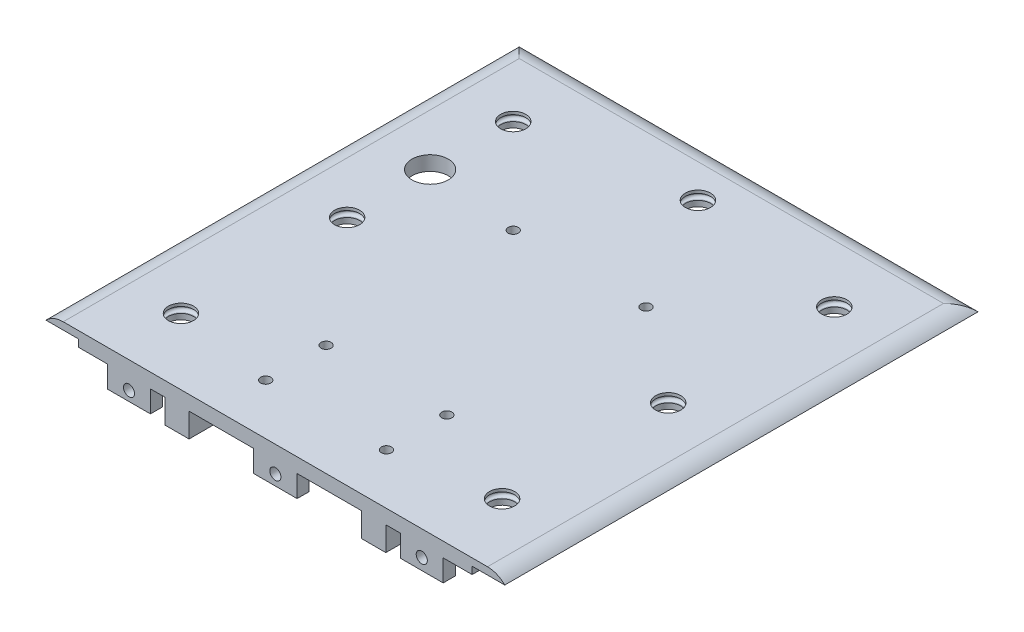
SolidWorks part; units mm, degrees
ref_plane "Спереди" through (0, 0, 0) normal (0, 0, 1) x (1, 0, 0)
ref_plane "Сверху" through (0, 0, 0) normal (0, 1, 0) x (1, 0, 0)
ref_plane "Справа" through (0, 0, 0) normal (1, 0, 0) x (0, 0, -1)
sketch "Эскиз1" plane through (0, 0, 0) normal (0, 1, 0) x (1, 0, 0)
  line L1 (0, 0) -> (190, 0)
  line L2 (0, 0) -> (0, 196)
  line L3 (0, 196) -> (190, 196)
  line L4 (190, 0) -> (190, 196)
  dimension "D1" = 196
  dimension "D2" = 190
extrude "Бобышка-Вытянуть1" add sketch "Эскиз1" along normal blind 3
fillet "Скругление1" radius 10 3 edges at (95, 3, -196) (190, 3, -98) (0, 3, -98)
sketch "Эскиз2" plane through (0, 0, 0) normal (0, -1, 0) x (1, 0, 0)
  line L1 (13.5, 0) -> (176.5, 0)
  line L2 (13.5, 0) -> (13.5, -187)
  line L3 (13.5, -187) -> (176.5, -187)
  line L4 (176.5, 0) -> (176.5, -187)
  line L5 (0, 0) -> (13.5, 0) construction
  line L6 (176.5, 0) -> (190, 0) construction
  dimension "D1" = 163
  dimension "D2" = 187
extrude "Бобышка-Вытянуть2" add sketch "Эскиз2" along normal blind 3
sketch "Эскиз3" plane through (0, -3, 0) normal (0, -1, 0) x (1, 0, 0)
  line L4 (54.25, 0) -> (54.25, -108.85) construction
  line L5 (135.75, 0) -> (135.75, -108.85) construction
  line L7 (49.25, -108.85) -> (59.25, -108.85)
  line L8 (49.25, -108.85) -> (49.25, 0)
  line L9 (49.25, 0) -> (59.25, 0)
  line L10 (59.25, -108.85) -> (59.25, 0)
  line L11 (49.25, -108.85) -> (59.25, 0) construction
  line L12 (49.25, 0) -> (59.25, -108.85) construction
  line L19 (130.75, -108.85) -> (140.75, -108.85)
  line L20 (130.75, -108.85) -> (130.75, 0)
  line L21 (130.75, 0) -> (140.75, 0)
  line L22 (140.75, -108.85) -> (140.75, 0)
  line L23 (130.75, -108.85) -> (140.75, 0) construction
  line L24 (130.75, 0) -> (140.75, -108.85) construction
  point P13 (54.25, -54.425)
  point P22 (135.75, -54.425)
  dimension "D1" = 108.85
  dimension "D2" = 10
extrude "Бобышка-Вытянуть3" add sketch "Эскиз3" along normal blind 10
sketch "Эскиз4" plane through (0, -3, 0) normal (0, -1, 0) x (1, 0, 0)
  line L0 (49.25, 0) -> (13.5, 0) construction
  line L1 (43.25, 0) -> (25.5, 0)
  line L2 (43.25, 0) -> (43.25, -5)
  line L3 (43.25, -5) -> (25.5, -5)
  line L4 (25.5, 0) -> (25.5, -5)
  line L11 (130.75, 0) -> (59.25, 0) construction
  line L12 (86, 0) -> (104, 0)
  line L13 (86, 0) -> (86, -5)
  line L14 (86, -5) -> (104, -5)
  line L15 (104, 0) -> (104, -5)
  line L16 (176.5, 0) -> (140.75, 0) construction
  line L17 (146.75, 0) -> (164.5, 0)
  line L18 (146.75, 0) -> (146.75, -5)
  line L19 (146.75, -5) -> (164.5, -5)
  line L20 (164.5, 0) -> (164.5, -5)
  line L22 (140.75, -108.85) -> (140.75, 0) construction
  line L23 (130.75, 0) -> (130.75, -108.85) construction
  line L27 (49.25, 0) -> (49.25, -108.85) construction
  line L28 (13.5, 0) -> (13.5, -187) construction
  line L29 (176.5, -187) -> (176.5, 0) construction
  dimension "D1" = 5
  dimension "D2" = 6
  dimension "D3" = 26.75
  dimension "D4" = 18
  dimension "D7" = 6
  dimension "D8" = 12
  dimension "D9" = 12
extrude "Бобышка-Вытянуть4" add sketch "Эскиз4" along normal blind 9
sketch "Эскиз5" plane through (0, 0, 0) normal (0, 0, 1) x (1, 0, 0)
  line L0 (34.375, -12) -> (34.375, -8) construction
  line L1 (43.25, -12) -> (25.5, -12) construction
  line L2 (34.375, -8) -> (161.3004, -7.2587) construction
  line L3 (155.625, -12) -> (155.625, -7.2919) construction
  line L4 (164.5, -12) -> (146.75, -12) construction
  line L5 (95, -12) -> (95, -7.6459) construction
  line L6 (104, -12) -> (86, -12) construction
  circle A1 centre (95, -7.6459) radius 2.3
  circle A2 centre (155.625, -7.2919) radius 2.3
  circle A3 centre (34.375, -8) radius 2.3
  dimension "D1" = 4.6
  dimension "D2" = 4
extrude "Вырез-Вытянуть1" cut sketch "Эскиз5" against normal blind 9
sketch "Эскиз6" plane through (49.25, 0, 0) normal (-1, 0, 0) x (0, 0, 1)
  line L0 (-108.85, -13) -> (-108.85, -9) construction
  line L1 (-108.85, -13) -> (-108.85, -3) construction
  line L2 (-108.85, -9) -> (-93.85, -9) construction
  circle A0 centre (-93.85, -9) radius 2.3
  circle A1 centre (-53.85, -9) radius 2.3
  circle A3 centre (-13.85, -9) radius 2.3 [skipped]
  dimension "D3" = 4.6
  dimension "D1" = 4
  dimension "D2" = 15
  dimension "D4" = 3
extrude "Вырез-Вытянуть2" cut sketch "Эскиз6" against normal blind 230
fillet "Скругление2" radius 2 1 edges at (95, -3, -187)
sketch "Эскиз8" plane through (0, -3, 0) normal (0, -1, 0) x (1, 0, 0)
  line L0 (95, -185) -> (95, -175) construction
  line L1 (13.5, -185) -> (176.5, -185) construction
  line L2 (13.5, -165) -> (28.5, -165) construction
  line L3 (13.5, 0) -> (13.5, -187) construction
  line L4 (13.5, -96.2) -> (28.5, -96.2) construction
  line L5 (13.5, 0) -> (13.5, -185) construction
  line L6 (13.5, -27.4) -> (28.5, -27.4) construction
  line L7 (176.5, -27.4) -> (161.5, -27.4) construction
  line L8 (176.5, -185) -> (176.5, 0) construction
  line L9 (176.5, -96.2) -> (161.5, -96.2) construction
  line L10 (176.5, -187) -> (176.5, 0) construction
  line L11 (176.5, -165) -> (161.5, -165) construction
  circle A0 centre (28.5, -27.4) radius 5.2
  circle A1 centre (28.5, -96.2) radius 5.2
  circle A2 centre (28.5, -165) radius 5.2
  circle A3 centre (95, -175) radius 5.2
  circle A4 centre (161.5, -165) radius 5.2
  circle A5 centre (161.5, -96.2) radius 5.2
  circle A6 centre (161.5, -27.4) radius 5.2
  dimension "D5" = 10.4
  dimension "D1" = 20
  dimension "D2" = 10
  dimension "D3" = 68.8
  dimension "D4" = 68.8
  dimension "D6" = 20
  dimension "D7" = 15
extrude "Вырез-Вытянуть3" cut sketch "Эскиз8" against normal blind 10
sketch "Эскиз9" plane through (0, 3, 0) normal (0, 1, 0) x (1, 0, 0)
  circle A0 centre (28.5, 27.4) radius 6.7
  circle A1 centre (28.5, 96.2) radius 6.7
  circle A2 centre (28.5, 165) radius 6.7
  circle A3 centre (95, 175) radius 6.7
  circle A4 centre (161.5, 165) radius 6.7
  circle A5 centre (161.5, 96.2) radius 6.7
  circle A6 centre (161.5, 27.4) radius 6.7
  dimension "D1" = 13.4
extrude "Вырез-Вытянуть4" cut sketch "Эскиз9" against normal blind 2.5 from offset 1.2 offset against normal yes
fillet "Скругление3" radius 1.2 14 edges at (161.5, 1.8, -89.5) (161.5, 1.8, -158.3) (95, 1.8, -168.3) (28.5, 1.8, -158.3) (28.5, 1.8, -89.5) (28.5, 1.8, -20.7) (161.5, 1.8, -20.7) (28.5, -0.7, -20.7) (28.5, -0.7, -89.5) (28.5, -0.7, -158.3) (95, -0.7, -168.3) (161.5, -0.7, -158.3) (161.5, -0.7, -89.5) (161.5, -0.7, -20.7)
sketch "Эскиз10" plane through (0, 0, 0) normal (0, -1, 0) x (1, 0, 0)
  line L0 (13.5, 0) -> (9.5, 0) construction
  line L1 (0, 0) -> (13.5, 0) construction
  line L2 (95, -187) -> (95, -191) construction
  line L3 (13.5, -187) -> (176.5, -187) construction
  line L4 (176.5, 0) -> (180.5, 0) construction
  line L5 (9.5, 0) -> (9.5, -185)
  line L6 (15.5, -191) -> (174.5, -191)
  line L7 (180.5, -185) -> (180.5, 0)
  arc A0 (9.5, -185) -> (15.5, -191) centre (15.5, -185) ccw
  arc A1 (174.5, -191) -> (180.5, -185) centre (174.5, -185) ccw
  dimension "D2" = 6
  dimension "D1" = 4
sketch "Эскиз11" plane through (0, 0, 0) normal (0, 0, 1) x (1, 0, 0)
  line L0 (9.5, 0) -> (9.5, -0.15) construction
  line L1 (13.5, 0) -> (9.5, 0) construction
  line L2 (9.5, 0) -> (15.5, 0) construction
  circle A0 centre (9.5, -0.15) radius 1.35
  dimension "D1" = 2.7
  dimension "D2" = 0.15
sweep "Вырез-По траектории1" [suppressed] cut profiles "Эскиз11" path "Эскиз10"
sketch "Эскиз12" plane through (0, -3, 0) normal (0, -1, 0) x (1, 0, 0)
  line L0 (28.5, -165) -> (28.5, -96.2) construction
  circle A0 centre (28.5, -130.6) radius 7.5
  point P9 (28.5, -130.6)
  dimension "D1" = 15
extrude "Вырез-Вытянуть5" cut sketch "Эскиз12" against normal blind 10
sketch "Эскиз13" plane through (0, 3, 0) normal (0, 1, 0) x (1, 0, 0)
  line L0 (95, 196) -> (95, 126) construction
  line L1 (190, 196) -> (0, 196) construction
  line L2 (67.5, 126) -> (122.5, 126) construction
  line L3 (95, 126) -> (95, 46) construction
  line L4 (95, 46) -> (95, 21) construction
  line L5 (70, 21) -> (120, 21) construction
  line L6 (70, 46) -> (120, 46) construction
  circle A0 centre (67.5, 126) radius 2.1
  circle A1 centre (122.5, 126) radius 2.1
  circle A2 centre (70, 46) radius 2.1
  circle A3 centre (70, 21) radius 2.1
  circle A4 centre (120, 21) radius 2.1
  circle A5 centre (120, 46) radius 2.1
  point P7 (95, 126)
  point P14 (95, 21)
  point P17 (95, 46)
  dimension "D3" = 4.2
  dimension "D5" = 4.2
  dimension "D1" = 55
  dimension "D2" = 70
  dimension "D4" = 50
  dimension "D6" = 25
  dimension "D7" = 80
extrude "Вырез-Вытянуть6" cut sketch "Эскиз13" against normal blind 5
